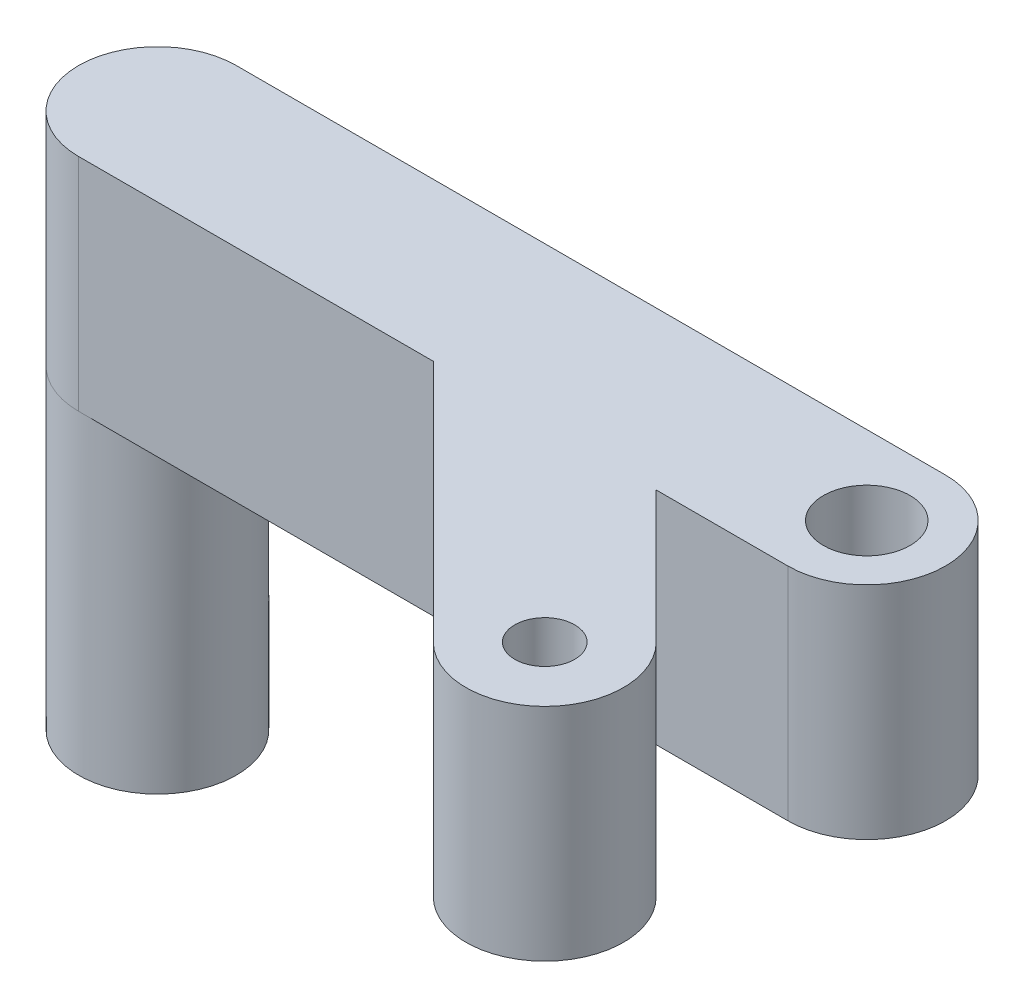
SolidWorks part; units mm, degrees
ref_plane "Front Plane" through (0, 0, 0) normal (0, 0, 1) x (1, 0, 0)
ref_plane "Top Plane" through (0, 0, 0) normal (0, 1, 0) x (1, 0, 0)
ref_plane "Right Plane" through (0, 0, 0) normal (1, 0, 0) x (0, 0, -1)
sketch "Sketch1" plane through (0, 0, 0) normal (0, 1, 0) x (1, 0, 0)
  circle A0 centre (0, 0) radius 2.75
  circle A1 centre (0, 0) radius 5
  dimension "D1" = 5.5
  dimension "D2" = 10
extrude "Boss-Extrude1" add sketch "Sketch1" along normal blind 14
sketch "Sketch2" plane through (0, 14, 0) normal (0, 1, 0) x (1, 0, 0)
  line L0 (0, 5) -> (-50, 5)
  line L1 (-50, 5) -> (-50, -5)
  line L2 (-50, -5) -> (0, -5)
  circle A0 centre (0, 0) radius 5 construction
  arc A1 (0, -5) -> (0, 5) centre (0, 0) cw
  point P7 (0, 0)
  point P8 (0, 0)
  point P10 (0, 0)
  point P11 (0, 0)
  point P12 (0, 0)
  dimension "D1" = 50
extrude "Boss-Extrude2" add sketch "Sketch2" against normal up to surface (14 mm away) up to face at (0, 0, 5)
sketch "Sketch3" plane through (0, 0, 0) normal (0, -1, 0) x (1, 0, 0)
  line L5 (-50, 5) -> (-50, -5) construction
  circle A1 centre (-45, 0) radius 5
  point P5 (0, 0)
  point P6 (-44.7097, -4.3682)
  point P7 (-50, 0)
  dimension "D1" = 10
extrude "Boss-Extrude3" add sketch "Sketch3" along normal blind 20
fillet "Fillet2" radius 5 2 edges at (-50, 7, -5) (-50, 7, 5)
sketch "Sketch4" plane through (0, 14, 0) normal (0, 1, 0) x (1, 0, 0)
  line L0 (-8.3579, -5) -> (0, -13.3579)
  line L1 (-45, -5) -> (0, -5) construction
  line L3 (-7.0711, -20.4289) -> (-22.5, -5)
  line L4 (-22.5, -5) -> (-8.3579, -5)
  arc A0 (-7.0711, -20.4289) -> (0, -13.3579) centre (-3.5355, -16.8934) ccw
  point P4 (-7.2095, -20.8053)
  point P7 (0, -20.8711)
  point P8 (0, -13.9902)
  point P9 (-22.5, -5)
  dimension "D2" = 5
  dimension "D1" = 10
  dimension "D3" = 135
extrude "Boss-Extrude4" add sketch "Sketch4" against normal up to surface (14 mm away) up to face at (-20, 0, 0)
sketch "Sketch5" plane through (0, 14, 0) normal (0, 1, 0) x (1, 0, 0)
  circle A0 centre (-3.5355, -16.8934) radius 1.9
  arc A1 (-7.0711, -20.4289) -> (0, -13.3579) centre (-3.5355, -16.8934) ccw construction
  dimension "D1" = 3.8
extrude "Cut-Extrude1" cut sketch "Sketch5" against normal through all
